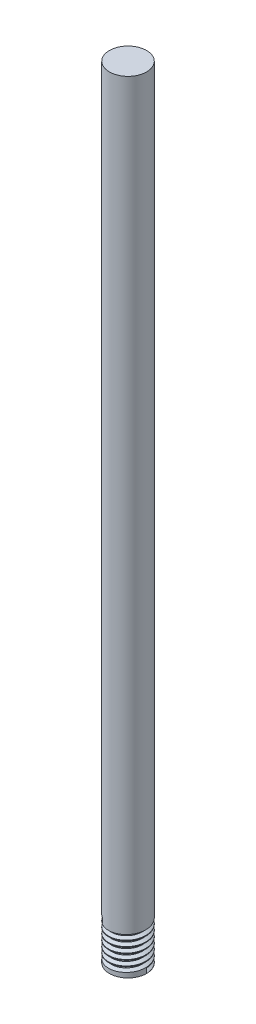
SolidWorks part; units mm, degrees
ref_plane "Front Plane" through (0, 0, 0) normal (0, 0, 1) x (1, 0, 0)
ref_plane "Top Plane" through (0, 0, 0) normal (0, 1, 0) x (1, 0, 0)
ref_plane "Right Plane" through (0, 0, 0) normal (1, 0, 0) x (0, 0, -1)
sketch "Sketch1" plane through (0, 0, 0) normal (0, 1, 0) x (1, 0, 0)
  circle A0 centre (-21.2841, 2.182) radius 5
  dimension "D1" = 10
extrude "Boss-Extrude1" add sketch "Sketch1" along normal blind 210
thread "Thread2" pitch 1.5 method cut profile "Thread Profile2" start angle 0, offset 0, length 10, pitch 1.5, diameter 10
ref_plane "Plane2" through (-16.2841, 0, -2.182) normal (0, 0, 1) x (1, 0, 0)
sketch "Thread Profile2" plane through (-16.2841, 0, -2.182) normal (0, 0, 1) x (1, 0, 0)
  line L0 (0, 0) -> (0, 1.5) construction
  line L11 (0, 0) -> (0, 1.3125)
  line L12 (0, 1.3125) -> (-0.8119, 0.8437)
  line L13 (-0.8119, 0.8437) -> (-0.8119, 0.4687)
  line L15 (-0.8119, 0.4687) -> (0, 0)
  line L17 (-0.8119, 0.6562) -> (0, 0.6562) construction
  point P2 (0, 0)
  dimension "Pitch" = 1.5
  dimension "Profile_Angle" = 60
  dimension "Profile_Land" = 0.375
  dimension "Profile_Height" = 0.8119
